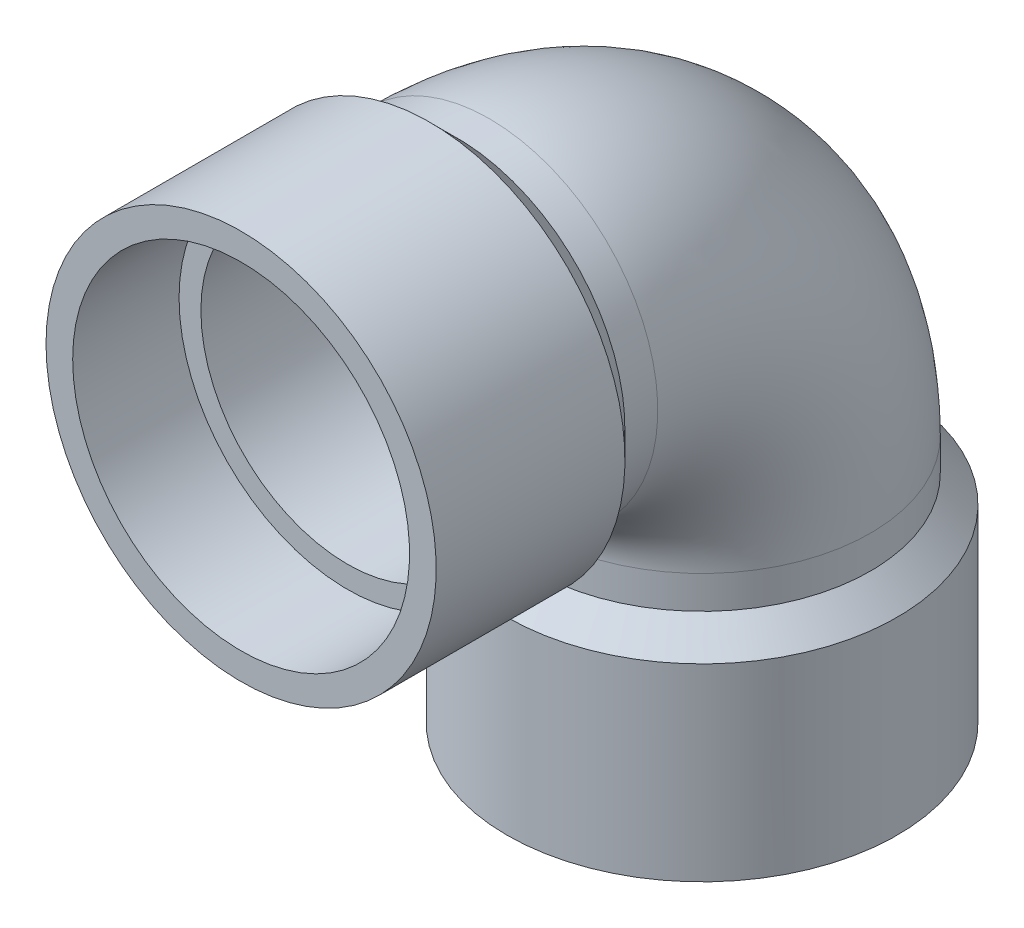
SolidWorks part; units mm, degrees
other "Published References"
other "Connector1"
other "Connector2"
ref_plane "Front Plane" through (0, 0, 0) normal (0, 0, 1) x (1, 0, 0)
ref_plane "Top Plane" through (0, 0, 0) normal (0, 1, 0) x (1, 0, 0)
ref_plane "Right Plane" through (0, 0, 0) normal (1, 0, 0) x (0, 0, -1)
sketch "Sketch1" plane through (0, 0, 0) normal (1, 0, 0) x (0, 0, -1)
  line L0 (-38.1, 0) -> (-63.5, 0)
  line L1 (0, -38.1) -> (0, -63.5)
  arc A0 (-38.1, 0) -> (0, -38.1) centre (-38.1, -38.1) cw
  point P6 (0, 0)
  dimension "D3" = 38.1
  dimension "D1" = 63.5
  dimension "D2" = 63.5
ref_plane "Plane1" through (0, 0, 63.5) normal (0, 0, 1) x (1, 0, 0)
sketch "Sketch2" plane through (0, 0, 63.5) normal (0, 0, 1) x (1, 0, 0)
  circle A0 centre (0, 0) radius 26.2509
  circle A1 centre (0, 0) radius 30.1625
  dimension "D1" = 52.5018
  dimension "D2" = 60.325
sweep "Sweep2" add profiles "Sketch2" path "Sketch1"
sketch "Sketch9" plane through (0, 0, 63.5) normal (0, 0, 1) x (1, 0, 0)
  circle A0 centre (0, 0) radius 34.9377
  circle A1 centre (0, 0) radius 30.1625
  dimension "D1" = 60.325
  dimension "D2" = 4.7752
extrude "Boss-Extrude1" add sketch "Sketch9" against normal blind 9.525 and the other way blind 19.05
ref_axis "Axis1" through (-40.1638, 0, 0) along (1, 0, 0)
ref_plane "Plane2" through (0, 0, 0) normal (0, 0.7071, 0.7071) x (1, 0, 0)
mirror "Mirror4" about plane through (0, 0, 0) normal (0, 0.7071, 0.7071) of "Boss-Extrude1"
chamfer "Chamfer1" distance 10 angle 45 2 edges at (30.1625, 0, 53.975) (30.1625, -53.975, 0)
